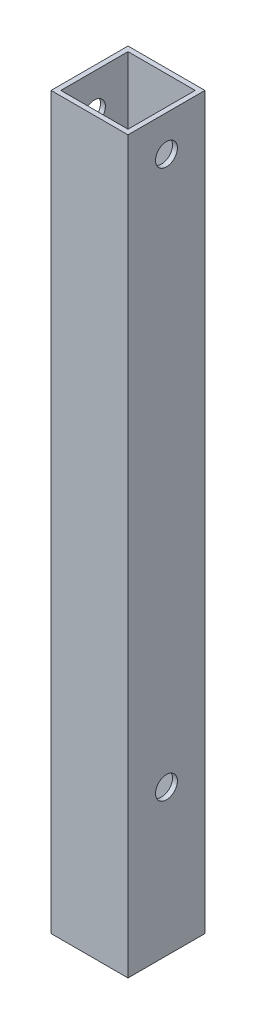
SolidWorks part; units mm, degrees
ref_plane "Front Plane" through (0, 0, 0) normal (0, 0, 1) x (1, 0, 0)
ref_plane "Top Plane" through (0, 0, 0) normal (0, 1, 0) x (1, 0, 0)
ref_plane "Right Plane" through (0, 0, 0) normal (1, 0, 0) x (0, 0, -1)
sketch "Sketch1" plane through (0, 0, 0) normal (0, 1, 0) x (1, 0, 0)
  line L0 (-6.9, -6.9) -> (-6.9, 6.9)
  line L1 (-7.9, -7.9) -> (7.9, -7.9)
  line L2 (-7.9, -7.9) -> (-7.9, 7.9)
  line L3 (-7.9, 7.9) -> (7.9, 7.9)
  line L4 (7.9, -7.9) -> (7.9, 7.9)
  line L5 (-7.9, -7.9) -> (7.9, 7.9) construction
  line L6 (-7.9, 7.9) -> (7.9, -7.9) construction
  line L7 (-6.9, 6.9) -> (6.9, 6.9)
  line L8 (6.9, -6.9) -> (6.9, 6.9)
  line L9 (-6.9, -6.9) -> (6.9, -6.9)
  point P0 (0, 0)
  dimension "D1" = 1
extrude "Boss-Extrude1" add sketch "Sketch1" along normal blind 150
sketch "Sketch2" plane through (-7.9, 0, 0) normal (-1, 0, 0) x (0, 0, 1)
  line L0 (-7.9, 150) -> (7.9, 150) construction
  line L1 (6.9, 0) -> (-6.9, 0) construction
  circle A0 centre (0, 142.6) radius 2.25
  circle A1 centre (0, 30) radius 2.25
  dimension "D1" = 4.5
  dimension "D2" = 7.4
  dimension "D3" = 4.5
  dimension "D4" = 30
extrude "Cut-Extrude1" cut sketch "Sketch2" against normal through all
